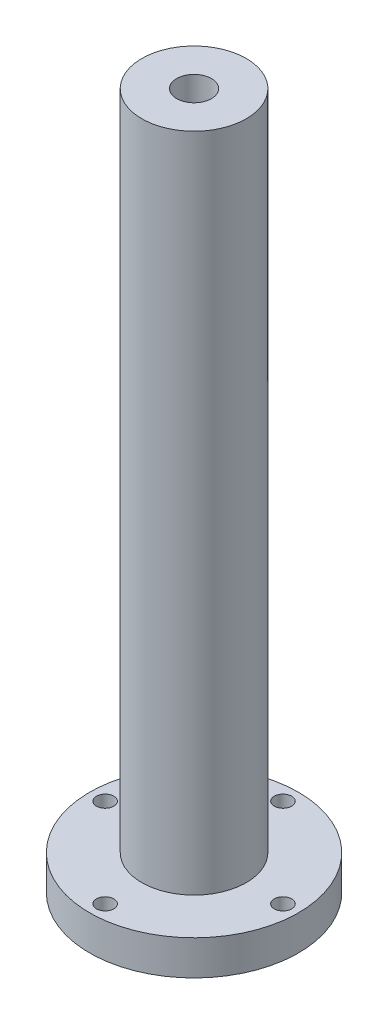
SolidWorks part; units mm, degrees
ref_plane "Front Plane" through (0, 0, 0) normal (0, 0, 1) x (1, 0, 0)
ref_plane "Top Plane" through (0, 0, 0) normal (0, 1, 0) x (1, 0, 0)
ref_plane "Right Plane" through (0, 0, 0) normal (1, 0, 0) x (0, 0, -1)
other "Center of Mass"
sketch "Sketch4" plane through (0, 0, 0) normal (0, 0, 1) x (1, 0, 0)
  line L1 (0, -1654.5442) -> (300, -1654.5442)
  line L2 (300, -1654.5442) -> (300, -1554.5442)
  line L3 (300, -1554.5442) -> (150, -1554.5442)
  line L11 (0, -1654.5442) -> (0, 382.6571) construction
  line L12 (0, -1654.5442) -> (0, 245.4558)
  line L13 (0, 245.4558) -> (50, 245.4558)
  line L14 (50, 245.4558) -> (50, 345.4558)
  line L17 (150, -1554.5442) -> (150, 345.4558)
  line L18 (150, 345.4558) -> (50, 345.4558)
  dimension "D1" = 300
  dimension "D2" = 100
  dimension "D3" = 150
  dimension "D4" = 50
  dimension "D5" = 2000
  dimension "D6" = 100
revolve "Revolve2" add sketch "Sketch4" angle 360 about L11
sketch "Sketch5" plane through (0, -1554.5442, 0) normal (0, 1, 0) x (1, 0, 0)
  circle A0 centre (0, 255.3655) radius 25
  circle A2 centre (255.3655, 0) radius 25
  circle A3 centre (0, -255.3655) radius 25
  circle A4 centre (-255.3655, 0) radius 25
  dimension "D1" = 4
  dimension "D2" = 50
extrude "Cut-Extrude2" cut sketch "Sketch5" against normal blind 100
ref_axis "Body_Axis" through (0, 445.4558, 0) along (0, -1, 0)
